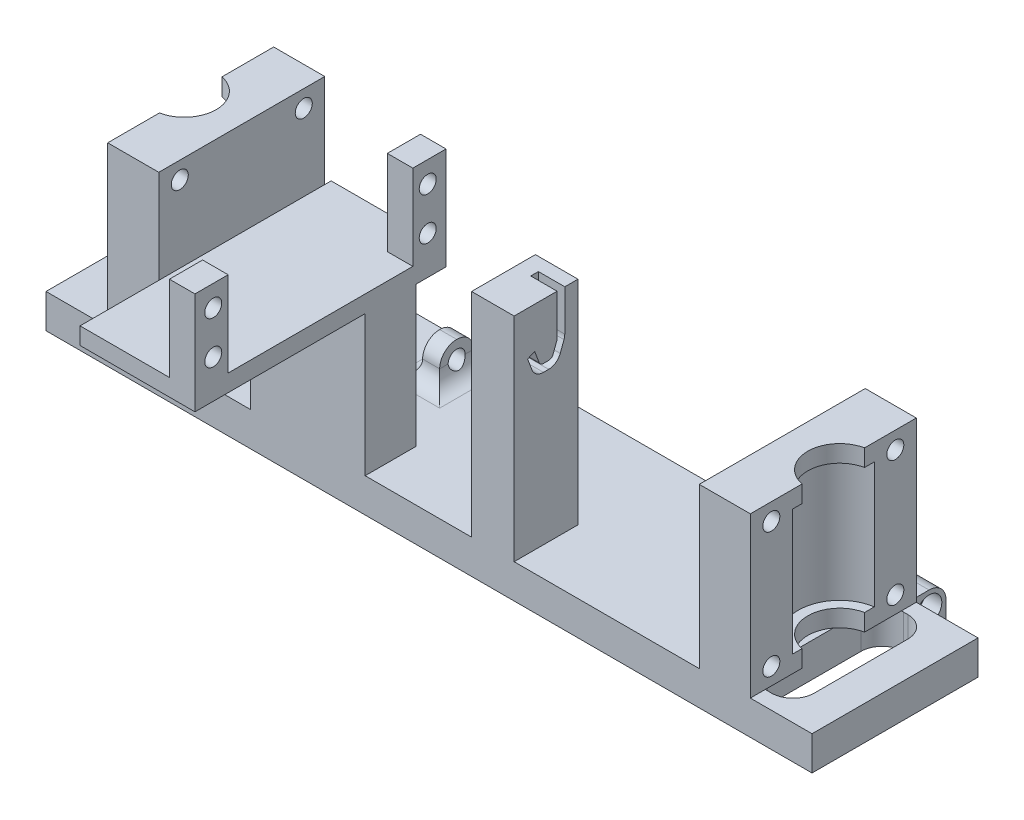
SolidWorks part; units mm, degrees
ref_plane "Plan de face" through (0, 0, 0) normal (0, 0, 1) x (1, 0, 0)
ref_plane "Plan de dessus" through (0, 0, 0) normal (0, 1, 0) x (1, 0, 0)
ref_plane "Plan de droite" through (0, 0, 0) normal (1, 0, 0) x (0, 0, -1)
sketch "Esquisse1" plane through (0, 0, 0) normal (0, 1, 0) x (1, 0, 0)
  line L0 (90, 39) -> (90, 0) construction
  line L1 (0, 0) -> (180, 0)
  line L2 (0, 0) -> (0, 39)
  line L3 (0, 39) -> (15.5, 39)
  line L6 (15.5, 39) -> (15.5, 47)
  line L7 (15.5, 47) -> (23.5, 47)
  line L14 (13, 35.5) -> (14, 35.5)
  line L15 (8, 30.5) -> (8, 8.5)
  line L16 (13, 3.5) -> (14, 3.5)
  line L17 (19, 30.5) -> (19, 8.5)
  line L24 (28.5, 47) -> (32.5, 47)
  line L25 (32.5, 39) -> (32.5, 47)
  line L26 (32.5, 39) -> (147.5, 39)
  line L27 (151.5, 47) -> (151.5, 38)
  line L29 (23.5, 47) -> (23.5, 38)
  line L30 (23.5, 38) -> (28.5, 38)
  line L31 (28.5, 47) -> (28.5, 38)
  line L32 (156.5, 38) -> (151.5, 38)
  line L33 (156.5, 47) -> (156.5, 38)
  line L34 (147.5, 39) -> (147.5, 47)
  line L35 (151.5, 47) -> (147.5, 47)
  line L36 (161, 30.5) -> (161, 8.5)
  line L37 (167, 3.5) -> (166, 3.5)
  line L38 (172, 30.5) -> (172, 8.5)
  line L39 (167, 35.5) -> (166, 35.5)
  line L40 (164.5, 47) -> (156.5, 47)
  line L41 (164.5, 39) -> (164.5, 47)
  line L42 (180, 39) -> (164.5, 39)
  line L43 (180, 0) -> (180, 39)
  arc A0 (8, 8.5) -> (13, 3.5) centre (13, 8.5) ccw
  arc A1 (14, 3.5) -> (19, 8.5) centre (14, 8.5) ccw
  arc A2 (14, 35.5) -> (19, 30.5) centre (14, 30.5) cw
  arc A3 (13, 35.5) -> (8, 30.5) centre (13, 30.5) ccw
  arc A8 (167, 35.5) -> (172, 30.5) centre (167, 30.5) cw
  arc A9 (166, 35.5) -> (161, 30.5) centre (166, 30.5) ccw
  arc A10 (166, 3.5) -> (161, 8.5) centre (166, 8.5) cw
  arc A11 (172, 8.5) -> (167, 3.5) centre (167, 8.5) cw
  point P23 (19, 3.5)
  point P26 (19, 35.5)
  point P29 (8, 35.5)
  point P51 (172, 35.5)
  point P52 (161, 35.5)
  point P53 (161, 3.5)
  dimension "D7" = 5
  dimension "D2" = 39
  dimension "D3" = 11
  dimension "D4" = 32
  dimension "D5" = 8
  dimension "D6" = 3.5
  dimension "D8" = 15.5
  dimension "D9" = 8
  dimension "D10" = 5
  dimension "D11" = 4
  dimension "D12" = 17
  dimension "D13" = 9
  dimension "D14" = 90
extrude "Boss.-Extru.1" add sketch "Esquisse1" along normal blind 8
sketch "Esquisse2" plane through (0, 8, 0) normal (0, 1, 0) x (1, 0, 0)
  line L0 (0, 0) -> (180, 0) construction
  line L1 (48, 0) -> (75, 0)
  line L2 (48, 0) -> (48, 12)
  line L3 (48, 12) -> (75, 12)
  line L4 (75, 0) -> (75, 12)
  line L5 (90, 39) -> (90, 0) construction
  line L6 (147.5, 39) -> (32.5, 39) construction
  dimension "D1" = 27
  dimension "D2" = 12
  dimension "D3" = 15
extrude "Boss.-Extru.2" add sketch "Esquisse2" along normal blind 33
sketch "Esquisse3" plane through (0, 41, 0) normal (0, 1, 0) x (1, 0, 0)
  line L0 (48, 0) -> (75, 0) construction
  line L1 (48, 19) -> (75, 19)
  line L2 (48, 19) -> (48, -40)
  line L3 (48, -40) -> (75, -40)
  line L4 (75, 19) -> (75, -40)
  line L5 (48, 12) -> (48, 0) construction
  line L6 (75, 0) -> (75, 12) construction
  dimension "D1" = 19
  dimension "D2" = 59
extrude "Boss.-Extru.3" add sketch "Esquisse3" along normal blind 4
sketch "Esquisse4" plane through (75, 0, 0) normal (1, 0, 0) x (0, 0, -1)
  line L0 (-32.2, 55) -> (-40, 55) construction
  line L1 (19, 45) -> (11.2, 45)
  line L2 (19, 45) -> (19, 65)
  line L3 (19, 65) -> (11.2, 65)
  line L4 (11.2, 45) -> (11.2, 65)
  line L5 (-40, 45) -> (-32.2, 45)
  line L6 (-40, 45) -> (-40, 65)
  line L7 (-40, 65) -> (-32.2, 65)
  line L8 (-32.2, 45) -> (-32.2, 65)
  line L9 (-35.7, 60) -> (-35.7, 50) construction
  line L10 (-10.5, 45) -> (-10.5, 65) construction
  line L11 (-40, 45) -> (19, 45) construction
  circle A0 centre (-35.7, 60) radius 2
  circle A1 centre (-35.7, 50) radius 2
  circle A2 centre (14.7, 50) radius 2
  circle A3 centre (14.7, 60) radius 2
  point P16 (-35.7, 55)
  dimension "D5" = 4
  dimension "D1" = 20
  dimension "D2" = 43.4
  dimension "D3" = 10
  dimension "D4" = 3.5
extrude "Boss.-Extru.4" add sketch "Esquisse4" against normal blind 6
sketch "Esquisse6" plane through (164.5, 0, 0) normal (1, 0, 0) x (0, 0, -1)
  line L0 (47, 8) -> (39, 0) construction
  point P4 (43, 4)
sketch "Esquisse7" plane through (15.5, 0, 0) normal (-1, 0, 0) x (0, 0, 1)
  line L0 (-47, 8) -> (-39, 0) construction
  point P4 (-43, 4)
hole_wizard "Perçage1" positions "Esquisse3D1" profile "Esquisse8" legacy
sketch3d "Esquisse3D1"
  point P0 (15.5, 4, -43)
  point P4 (164.5, 4, -43)
sketch "Esquisse8" plane through (15.5, 4, -43) normal (0, 1, 0) x (0, 0, 1)
  line L0 (0, 0) -> (0, 17)
  line L1 (0, 17) -> (2, 17)
  line L2 (2, 17) -> (2, 4)
  line L3 (2, 4) -> (3, 4)
  line L4 (3, 4) -> (3, 0)
  line L5 (3, 0) -> (0, 0)
  line L6 (0, 110) -> (0, -10) construction
  dimension "Diamètre" = 4
  dimension "Profondeur" = 17
  dimension "Diamètre chambrage" = 6
  dimension "Profondeur chambrage" = 4
ref_plane "Plan2" through (66, 0, 0) normal (1, 0, 0) x (0, 0, -1)
sketch "Esquisse9" plane through (66, 0, 0) normal (1, 0, 0) x (0, 0, -1)
  line L0 (0, 8) -> (39, 8) construction
  line L1 (26.5, 8) -> (34.5, 8)
  line L2 (26.5, 8) -> (26.5, 16)
  line L3 (26.5, 16) -> (34.5, 16)
  line L4 (34.5, 8) -> (34.5, 16)
  line L5 (26.5, 16) -> (34.5, 8) construction
  line L6 (39, 8) -> (39, 0) construction
  circle A0 centre (30.5, 12) radius 2
  dimension "D2" = 4
  dimension "D1" = 8
  dimension "D3" = 4.5
extrude "Boss.-Extru.5" add sketch "Esquisse9" against normal blind 4
fillet "Congé1" radius 4 10 edges at (64, 8, -26.5) (62, 8, -30.5) (64, 8, -34.5) (66, 8, -30.5) (30.5, 8, -47) (19.5, 8, -47) (149.5, 8, -47) (160.5, 8, -47) (64, 16, -34.5) (64, 16, -26.5)
sketch "Esquisse13" plane through (0, 8, 0) normal (0, 1, 0) x (1, 0, 0)
  line L0 (15.5, 39) -> (0, 39) construction
  line L1 (14.5, 39) -> (26.5, 39)
  line L2 (14.5, 39) -> (14.5, 0) construction
  line L3 (14.5, 0) -> (26.5, 0)
  line L4 (26.5, 39) -> (26.5, 0)
  line L5 (0, 0) -> (48, 0) construction
  line L7 (14.5, 19.5) -> (13, 19.5) construction
  line L8 (14.5, 39) -> (14.5, 29.1339)
  line L9 (14.5, 9.8661) -> (14.5, 0)
  line L10 (90, 39) -> (90, 0) construction
  line L11 (147.5, 39) -> (32.5, 39) construction
  line L12 (75, 0) -> (180, 0) construction
  line L13 (165.5, 39) -> (165.5, 29.1339)
  line L14 (165.5, 39) -> (153.5, 39)
  line L15 (153.5, 39) -> (153.5, 0)
  line L16 (165.5, 0) -> (153.5, 0)
  line L17 (165.5, 9.8661) -> (165.5, 0)
  line L20 (23.5, 38) -> (23.5, 43) construction
  circle A0 centre (13, 19.5) radius 9.75 construction
  arc A1 (14.5, 29.1339) -> (14.5, 9.8661) centre (13, 19.5) cw
  arc A2 (165.5, 29.1339) -> (165.5, 9.8661) centre (167, 19.5) ccw
  dimension "D3" = 19.5
  dimension "D1" = 12
  dimension "D2" = 1.5
  dimension "D4" = 3
extrude "Boss.-Extru.8" add sketch "Esquisse13" along normal blind 37.5
sketch "Esquisse14" plane through (0, 45.5, 0) normal (0, 1, 0) x (1, 0, 0)
  line L0 (14.5, 19.5) -> (13, 19.5) construction
  line L1 (14.5, 39) -> (26.5, 39)
  line L2 (14.5, 39) -> (14.5, 0) construction
  line L3 (14.5, 0) -> (26.5, 0)
  line L4 (26.5, 39) -> (26.5, 0)
  line L5 (14.5, 39) -> (14.5, 26.8485)
  line L6 (14.5, 0) -> (14.5, 12.1515)
  line L7 (90, 39) -> (90, 0) construction
  line L8 (147.5, 39) -> (32.5, 39) construction
  line L9 (75, 0) -> (153.5, 0) construction
  line L10 (165.5, 39) -> (165.5, 26.8485)
  line L11 (165.5, 39) -> (153.5, 39)
  line L12 (153.5, 39) -> (153.5, 0)
  line L13 (165.5, 0) -> (153.5, 0)
  line L14 (165.5, 0) -> (165.5, 12.1515)
  line L16 (26.5, 0) -> (26.5, 38) construction
  line L17 (14.5, 0) -> (26.5, 0) construction
  circle A0 centre (13, 19.5) radius 7.5 construction
  arc A1 (14.5, 26.8485) -> (14.5, 12.1515) centre (13, 19.5) cw
  arc A2 (165.5, 26.8485) -> (165.5, 12.1515) centre (167, 19.5) ccw
  dimension "D2" = 15
  dimension "D1" = 1.5
extrude "Boss.-Extru.9" add sketch "Esquisse14" against normal blind 4
sketch "Esquisse15" plane through (0, 8, 0) normal (0, 1, 0) x (1, 0, 0)
  line L0 (14.5, 19.5) -> (13, 19.5) construction
  line L1 (14.5, 39) -> (26.5, 39)
  line L2 (14.5, 39) -> (14.5, 0) construction
  line L3 (14.5, 0) -> (26.5, 0)
  line L4 (26.5, 39) -> (26.5, 0)
  line L5 (14.5, 12.1515) -> (14.5, 0)
  line L6 (14.5, 39) -> (14.5, 26.8485)
  line L7 (90, 39) -> (90, 0) construction
  line L8 (147.5, 39) -> (32.5, 39) construction
  line L9 (75, 0) -> (153.5, 0) construction
  line L10 (165.5, 39) -> (165.5, 26.8485)
  line L11 (165.5, 39) -> (153.5, 39)
  line L12 (153.5, 39) -> (153.5, 0)
  line L13 (165.5, 0) -> (153.5, 0)
  line L14 (165.5, 12.1515) -> (165.5, 0)
  line L15 (26.5, 0) -> (26.5, 38) construction
  line L16 (14.5, 0) -> (26.5, 0) construction
  circle A0 centre (13, 19.5) radius 7.5 construction
  arc A1 (14.5, 26.8485) -> (14.5, 12.1515) centre (13, 19.5) cw
  arc A2 (165.5, 26.8485) -> (165.5, 12.1515) centre (167, 19.5) ccw
  dimension "D2" = 15
  dimension "D1" = 1.5
extrude "Boss.-Extru.10" add sketch "Esquisse15" along normal blind 4
sketch "Esquisse16" plane through (165.5, 0, 0) normal (1, 0, 0) x (0, 0, -1)
  line L0 (9.8661, 41.5) -> (0, 41.5) construction
  line L1 (0, 45.5) -> (0, 8) construction
  line L2 (9.8661, 12) -> (0, 12) construction
  line L3 (29.1339, 41.5) -> (39, 41.5) construction
  line L4 (39, 45.5) -> (39, 8) construction
  line L5 (29.1339, 12) -> (39, 12) construction
  circle A0 centre (4.933, 12) radius 2
  circle A1 centre (4.933, 41.5) radius 2
  circle A2 centre (34.067, 41.5) radius 2
  circle A3 centre (34.067, 12) radius 2
  dimension "D1" = 4
extrude "Enlèv. mat.-Extru.2" cut sketch "Esquisse16" against normal up to next
sketch "Esquisse17" plane through (14.5, 0, 0) normal (-1, 0, 0) x (0, 0, 1)
  line L0 (-29.1339, 41.5) -> (-39, 41.5) construction
  line L1 (-39, 45.5) -> (-39, 8) construction
  line L2 (-29.1339, 26.75) -> (-39, 26.75) construction
  line L3 (-29.1339, 41.5) -> (-29.1339, 12) construction
  line L4 (-19.5, 41.5) -> (-19.5, 12) construction
  line L5 (-29.1339, 41.5) -> (-9.8661, 41.5) construction
  line L6 (-12.1515, 12) -> (-26.8485, 12) construction
  circle A0 centre (-34.067, 41.5) radius 2
  circle A1 centre (-34.067, 12) radius 2
  circle A2 centre (-4.933, 12) radius 2
  circle A3 centre (-4.933, 41.5) radius 2
  dimension "D1" = 4
extrude "Enlèv. mat.-Extru.3" cut sketch "Esquisse17" against normal up to next
sketch "Esquisse18" plane through (0, 8, 0) normal (0, 1, 0) x (1, 0, 0)
  line L0 (75, 0) -> (153.5, 0) construction
  line L1 (100, 0) -> (110, 0)
  line L2 (100, 0) -> (100, 15)
  line L3 (100, 15) -> (110, 15)
  line L4 (110, 0) -> (110, 15)
  line L5 (147.5, 39) -> (32.5, 39) construction
  point P8 (90, 39)
  dimension "D1" = 10
  dimension "D2" = 10
  dimension "D3" = 15
extrude "Boss.-Extru.11" add sketch "Esquisse18" along normal blind 50
sketch "Esquisse19" plane through (110, 0, 0) normal (1, 0, 0) x (0, 0, -1)
  line L0 (11, 58) -> (11, 48.3627)
  line L1 (0, 58) -> (15, 58) construction
  line L2 (10.8727, 47.6604) -> (9.9867, 45.2978)
  line L3 (8.114, 44) -> (6.886, 44)
  line L4 (5.0133, 45.2978) -> (4, 48)
  line L5 (15, 58) -> (15, 8) construction
  line L6 (4, 48) -> (11, 48) construction
  line L7 (7.5, 44) -> (7.5, 48) construction
  line L8 (7.5, 58) -> (7.5, 48) construction
  arc A0 (11, 48.3627) -> (10.8727, 47.6604) centre (9, 48.3627) cw
  arc A1 (6.886, 44) -> (5.0133, 45.2978) centre (6.886, 46) cw
  arc A2 (9.9867, 45.2978) -> (8.114, 44) centre (8.114, 46) cw
  point P17 (5.5, 44)
  point P20 (9.5, 44)
  dimension "D5" = 2
  dimension "D1" = 10
  dimension "D2" = 4
  dimension "D3" = 4
  dimension "D4" = 4
sketch "Esquisse20" plane through (0, 58, 0) normal (0, 1, 0) x (1, 0, 0)
  line L0 (110, 0) -> (110, 15) construction
  line L1 (110, 11.9) -> (103.8, 11.9)
  line L2 (110, 11.9) -> (110, 10.1)
  line L3 (110, 10.1) -> (103.8, 10.1)
  line L4 (103.8, 11.9) -> (103.8, 10.1)
  line L5 (110, 15) -> (100, 15) construction
  point P8 (110, 11)
  dimension "D1" = 1.8
  dimension "D2" = 6.2
  dimension "D3" = 4
sweep "Enlèvement de matière-Balayage1" cut profiles "Esquisse20" path "Esquisse19"
